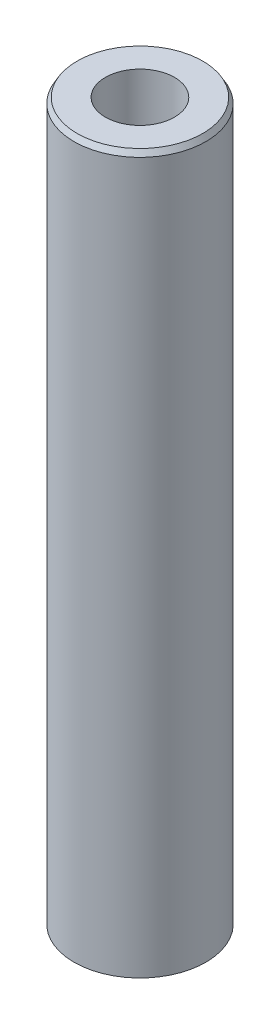
SolidWorks part; units mm, degrees
ref_plane "Front Plane" through (0, 0, 0) normal (0, 0, 1) x (1, 0, 0)
ref_plane "Top Plane" through (0, 0, 0) normal (0, 1, 0) x (1, 0, 0)
ref_plane "Right Plane" through (0, 0, 0) normal (1, 0, 0) x (0, 0, -1)
sketch "Sketch1" plane through (0, 0, 0) normal (0, 1, 0) x (1, 0, 0)
  circle A0 centre (0, 0) radius 55
  dimension "SHAFT_OD" = 110
extrude "Boss-Extrude1" add sketch "Sketch1" along normal blind 600
sketch "Sketch2" plane through (0, 0, 0) normal (0, 1, 0) x (1, 0, 0)
  circle A0 centre (0, 0) radius 28.8175
  dimension "BORE_D" = 57.635
extrude "Cut-Extrude1" cut sketch "Sketch2" along normal through all
chamfer "Chamfer1" distance 4.5494 angle 30 2 edges at (0, 600, 55) (0, 0, 55) first distance on face at (0, 600, 55) first distance on face at (0, 0, 28.8175)
